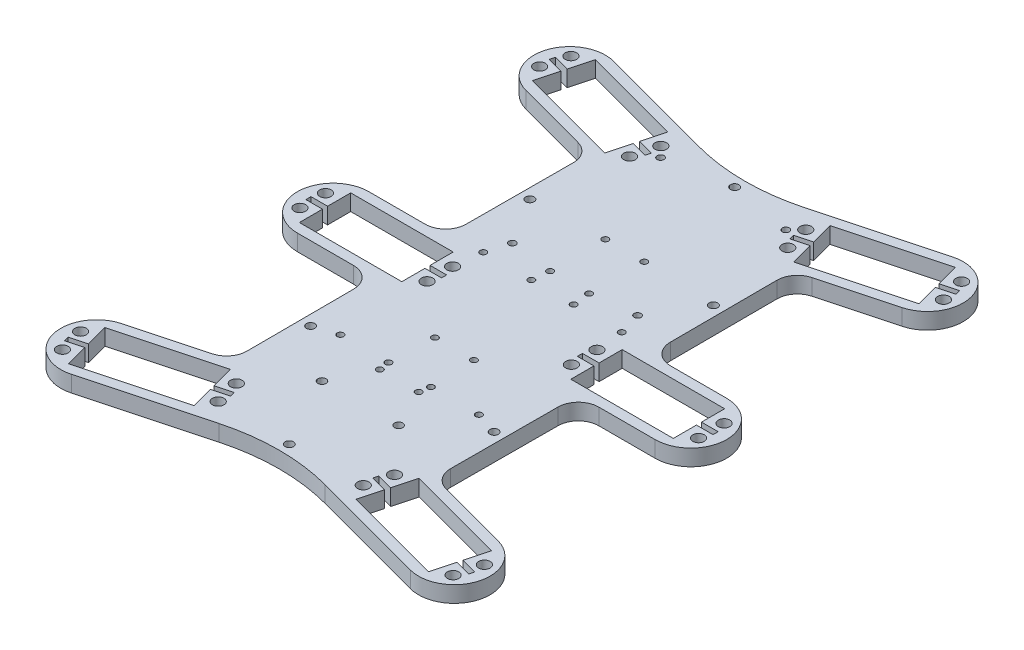
SolidWorks part; units mm, degrees
ref_plane "Front Plane" through (0, 0, 0) normal (0, 0, 1) x (1, 0, 0)
ref_plane "Top Plane" through (0, 0, 0) normal (0, 1, 0) x (1, 0, 0)
ref_plane "Right Plane" through (0, 0, 0) normal (1, 0, 0) x (0, 0, -1)
sketch "Sketch1" plane through (0, 0, 0) normal (0, 1, 0) x (1, 0, 0)
  line L0 (0, 32.1883) -> (0, -21.4181) construction
  line L1 (0, 0) -> (27.1703, 0) construction
  line L2 (-70, 14) -> (-40, 14)
  line L3 (-40, 14) -> (-39.8161, 70)
  line L4 (-39.8161, 70) -> (-73.6235, 79.0587)
  line L5 (-66.3765, 106.1046) -> (0, 88.3191)
  line L10 (-66.3765, 106.1046) -> (-73.6235, 79.0587) construction
  line L12 (-70, 14) -> (-70, -14) construction
  line L14 (-66.3765, -106.1046) -> (0, -88.3191)
  line L15 (-39.8161, -70) -> (-73.6235, -79.0587)
  line L16 (-40, -14) -> (-39.8161, -70)
  line L17 (-70, -14) -> (-40, -14)
  line L18 (66.3765, -106.1046) -> (0, -88.3191)
  line L19 (66.3765, 106.1046) -> (0, 88.3191)
  line L20 (70, 14) -> (70, -14) construction
  line L21 (66.3765, 106.1046) -> (73.6235, 79.0587) construction
  line L22 (70, -14) -> (40, -14)
  line L23 (40, -14) -> (39.8161, -70)
  line L24 (39.8161, -70) -> (73.6235, -79.0587)
  line L25 (39.8161, 70) -> (73.6235, 79.0587)
  line L26 (40, 14) -> (39.8161, 70)
  line L27 (70, 14) -> (40, 14)
  line L28 (-70.4609, 103.1096) -> (-75.6631, 83.6945)
  line L29 (-75.6631, 83.6945) -> (-36.9295, 73.3159)
  line L30 (-36.9295, 73.3159) -> (-31.7272, 92.731)
  line L31 (-31.7272, 92.731) -> (-70.4609, 103.1096)
  line L32 (-51.094, 97.9203) -> (-56.2963, 78.5052) construction
  line L33 (-70, 92.5816) -> (-73.062, 93.4021) construction
  line L34 (-53.12, 10.05) -> (-53.12, -10.05) construction
  line L35 (-73.17, 10.05) -> (-33.07, 10.05)
  line L36 (-73.17, 10.05) -> (-73.17, -10.05)
  line L37 (-73.17, -10.05) -> (-33.07, -10.05)
  line L38 (-33.07, 10.05) -> (-33.07, -10.05)
  line L39 (-73.17, 10.05) -> (-33.07, -10.05) construction
  line L40 (-73.17, -10.05) -> (-33.07, 10.05) construction
  line L41 (-36.9295, -73.3159) -> (-31.7272, -92.731)
  line L42 (-31.7272, -92.731) -> (-70.4609, -103.1096)
  line L43 (-70.4609, -103.1096) -> (-75.6631, -83.6945)
  line L44 (-75.6631, -83.6945) -> (-36.9295, -73.3159)
  line L45 (36.9295, 73.3159) -> (31.7272, 92.731)
  line L46 (75.6631, 83.6945) -> (36.9295, 73.3159)
  line L47 (70.4609, 103.1096) -> (75.6631, 83.6945)
  line L48 (31.7272, 92.731) -> (70.4609, 103.1096)
  line L49 (73.17, -10.05) -> (33.07, 10.05) construction
  line L50 (73.17, 10.05) -> (33.07, -10.05) construction
  line L51 (53.12, 10.05) -> (53.12, -10.05) construction
  line L52 (33.07, 10.05) -> (33.07, -10.05)
  line L53 (73.17, -10.05) -> (33.07, -10.05)
  line L54 (73.17, 10.05) -> (73.17, -10.05)
  line L55 (73.17, 10.05) -> (33.07, 10.05)
  line L56 (36.9295, -73.3159) -> (31.7272, -92.731)
  line L57 (75.6631, -83.6945) -> (36.9295, -73.3159)
  line L58 (31.7272, -92.731) -> (70.4609, -103.1096)
  line L59 (70.4609, -103.1096) -> (75.6631, -83.6945)
  line L60 (-76.4333, 99.4818) -> (-79.0215, 89.8226) construction
  line L61 (-77.7274, 94.6522) -> (-70, 92.5816) construction
  line L62 (-78, 5) -> (-78, -5) construction
  arc A0 (-70, 14) -> (-70, -14) centre (-70, 0) ccw
  arc A1 (-66.3765, 106.1046) -> (-73.6235, 79.0587) centre (-70, 92.5816) ccw
  circle A8 centre (-76.4333, 99.4818) radius 2.25
  circle A9 centre (-79.0215, 89.8226) radius 2.25
  circle A10 centre (-78, 5) radius 2.25
  arc A11 (-66.3765, -106.1046) -> (-73.6235, -79.0587) centre (-70, -92.5816) cw
  circle A12 centre (-79.0215, -89.8226) radius 2.25
  circle A13 centre (-76.4333, -99.4818) radius 2.25
  circle A14 centre (-78, -5) radius 2.25
  circle A15 centre (78, -5) radius 2.25
  circle A16 centre (76.4333, -99.4818) radius 2.25
  circle A17 centre (79.0215, -89.8226) radius 2.25
  arc A18 (66.3765, -106.1046) -> (73.6235, -79.0587) centre (70, -92.5816) ccw
  circle A19 centre (78, 5) radius 2.25
  circle A20 centre (79.0215, 89.8226) radius 2.25
  circle A21 centre (76.4333, 99.4818) radius 2.25
  arc A22 (66.3765, 106.1046) -> (73.6235, 79.0587) centre (70, 92.5816) cw
  arc A23 (70, 14) -> (70, -14) centre (70, 0) cw
  circle A24 centre (-30.957, 76.9437) radius 2.25
  circle A25 centre (-28.3688, 86.603) radius 2.25
  circle A26 centre (-28.24, -5) radius 2.25
  circle A27 centre (-28.24, 5) radius 2.25
  circle A28 centre (-28.3688, -86.603) radius 2.25
  circle A29 centre (-30.957, -76.9437) radius 2.25
  circle A30 centre (28.3688, 86.603) radius 2.25
  circle A31 centre (30.957, 76.9437) radius 2.25
  circle A32 centre (28.24, 5) radius 2.25
  circle A33 centre (28.24, -5) radius 2.25
  circle A34 centre (30.957, -76.9437) radius 2.25
  circle A35 centre (28.3688, -86.603) radius 2.25
  point P60 (-51.094, 97.9203)
  point P62 (-56.2963, 78.5052)
  point P65 (-73.062, 93.4021)
  point P71 (-53.12, 0)
  point P108 (53.12, 0)
  point P118 (-83.523, 96.2051)
  dimension "D2" = 14
  dimension "D3" = 10
  dimension "D8" = 4.5
  dimension "D1" = 75
  dimension "D4" = 70
  dimension "D5" = 30
  dimension "D6" = 35
  dimension "D7" = 56
  dimension "D9" = 8
  dimension "D10" = 5
  dimension "D11" = 10
  dimension "D12" = 40.1
  dimension "D13" = 20.1
  dimension "D14" = 4.83
  dimension "D15" = 40.1
  dimension "D16" = 20.1
  dimension "D17" = 4.83
  dimension "D18" = 8
extrude "Boss-Extrude1" add sketch "Sketch1" along normal blind 6.35
fillet "Fillet1" radius 80 2 edges at (0, 3.175, -88.3191) (0, 3.175, 88.3191)
fillet "Fillet2" radius 8 8 edges at (39.8161, 3.175, 70) (40, 3.175, 14) (40, 3.175, -14) (39.8161, 3.175, -70) (-39.8161, 3.175, -70) (-40, 3.175, -14) (-40, 3.175, 14) (-39.8161, 3.175, 70)
sketch "Sketch5" plane through (0, 6.35, 0) normal (0, 1, 0) x (1, 0, 0)
  line L0 (0, 91.1411) -> (0, -91.1411) construction
  line L1 (-84, 0) -> (84, 0) construction
  line L2 (-33.07, -10.05) -> (-33.07, 10.05) construction
  line L3 (-33.07, 1) -> (-26.57, 1)
  line L4 (-33.07, 1) -> (-33.07, -1)
  line L5 (-33.07, -1) -> (-26.57, -1)
  line L6 (-26.57, 1) -> (-26.57, -1)
  line L7 (-33.07, 1) -> (-26.57, -1) construction
  line L8 (-33.07, -1) -> (-26.57, 1) construction
  line L9 (-33.07, 10.05) -> (-73.17, 10.05) construction
  line L10 (-53.12, 10.05) -> (-53.12, -10.05) construction
  line L11 (-73.17, -10.05) -> (-33.07, -10.05) construction
  line L12 (-73.17, -1) -> (-79.67, 1) construction
  line L13 (-73.17, 1) -> (-79.67, -1) construction
  line L14 (-79.67, 1) -> (-79.67, -1)
  line L15 (-73.17, -1) -> (-79.67, -1)
  line L16 (-73.17, 1) -> (-73.17, -1)
  line L17 (-73.17, 1) -> (-79.67, 1)
  line L18 (-34.0695, 83.9894) -> (-27.791, 82.307)
  line L19 (-36.9295, 73.3159) -> (-31.7272, 92.731) construction
  line L20 (-27.791, 82.307) -> (-28.3087, 80.3752)
  line L21 (-28.3087, 80.3752) -> (-34.5872, 82.0575)
  line L22 (-34.0695, 83.9894) -> (-34.5872, 82.0575)
  line L23 (-51.094, 97.9203) -> (-56.2963, 78.5052) construction
  line L24 (-31.7272, 92.731) -> (-70.4609, 103.1096) construction
  line L25 (-75.6631, 83.6945) -> (-36.9295, 73.3159) construction
  line L26 (-72.8032, 94.368) -> (-73.3208, 92.4362)
  line L27 (-79.5993, 94.1185) -> (-73.3208, 92.4362)
  line L28 (-79.0817, 96.0503) -> (-79.5993, 94.1185)
  line L29 (-72.8032, 94.368) -> (-79.0817, 96.0503)
  line L30 (51.094, 97.9203) -> (56.2963, 78.5052) construction
  line L31 (72.8032, 94.368) -> (79.0817, 96.0503)
  line L32 (79.0817, 96.0503) -> (79.5993, 94.1185)
  line L33 (79.5993, 94.1185) -> (73.3208, 92.4362)
  line L34 (72.8032, 94.368) -> (73.3208, 92.4362)
  line L35 (34.0695, 83.9894) -> (34.5872, 82.0575)
  line L36 (28.3087, 80.3752) -> (34.5872, 82.0575)
  line L37 (27.791, 82.307) -> (28.3087, 80.3752)
  line L38 (34.0695, 83.9894) -> (27.791, 82.307)
  line L39 (73.17, 1) -> (79.67, -1) construction
  line L40 (73.17, -1) -> (79.67, 1) construction
  line L41 (53.12, 10.05) -> (53.12, -10.05) construction
  line L42 (33.07, -1) -> (26.57, 1) construction
  line L43 (33.07, 1) -> (26.57, -1) construction
  line L44 (73.17, 1) -> (79.67, 1)
  line L45 (73.17, 1) -> (73.17, -1)
  line L46 (73.17, -1) -> (79.67, -1)
  line L47 (79.67, 1) -> (79.67, -1)
  line L48 (26.57, 1) -> (26.57, -1)
  line L49 (33.07, -1) -> (26.57, -1)
  line L50 (33.07, 1) -> (33.07, -1)
  line L51 (33.07, 1) -> (26.57, 1)
  line L52 (51.094, -97.9203) -> (56.2963, -78.5052) construction
  line L53 (-51.094, -97.9203) -> (-56.2963, -78.5052) construction
  line L54 (34.0695, -83.9894) -> (27.791, -82.307)
  line L55 (27.791, -82.307) -> (28.3087, -80.3752)
  line L56 (28.3087, -80.3752) -> (34.5872, -82.0575)
  line L57 (34.0695, -83.9894) -> (34.5872, -82.0575)
  line L58 (72.8032, -94.368) -> (73.3208, -92.4362)
  line L59 (79.5993, -94.1185) -> (73.3208, -92.4362)
  line L60 (79.0817, -96.0503) -> (79.5993, -94.1185)
  line L61 (72.8032, -94.368) -> (79.0817, -96.0503)
  line L62 (-72.8032, -94.368) -> (-79.0817, -96.0503)
  line L63 (-79.0817, -96.0503) -> (-79.5993, -94.1185)
  line L64 (-79.5993, -94.1185) -> (-73.3208, -92.4362)
  line L65 (-72.8032, -94.368) -> (-73.3208, -92.4362)
  line L66 (-34.0695, -83.9894) -> (-34.5872, -82.0575)
  line L67 (-28.3087, -80.3752) -> (-34.5872, -82.0575)
  line L68 (-27.791, -82.307) -> (-28.3087, -80.3752)
  line L69 (-34.0695, -83.9894) -> (-27.791, -82.307)
  arc A0 (-20.7055, 93.8671) -> (20.7055, 93.8671) centre (0, 171.1411) ccw construction
  arc A1 (20.7055, -93.8671) -> (-20.7055, -93.8671) centre (0, -171.1411) ccw construction
  arc A2 (-70, 14) -> (-70, -14) centre (-70, 0) ccw construction
  arc A3 (70, -14) -> (70, 14) centre (70, 0) ccw construction
  point P16 (-29.82, 0)
  point P23 (-53.12, 10.05)
  point P34 (-76.42, 0)
  point P39 (-34.3284, 83.0234)
  point P42 (-34.3284, 83.0234)
  point P53 (-73.062, 93.4021)
  point P64 (73.062, 93.4021)
  point P65 (34.3284, 83.0234)
  point P76 (76.42, 0)
  point P77 (29.82, 0)
  point P98 (34.3284, -83.0234)
  point P99 (73.062, -93.4021)
  point P100 (-73.062, -93.4021)
  point P101 (-34.3284, -83.0234)
  dimension "D1" = 2
  dimension "D2" = 6.5
  dimension "D3" = 2
  dimension "D4" = 6.5
extrude "Cut-Extrude2" cut sketch "Sketch5" against normal through all
sketch "Sketch6" plane through (0, 6.35, 0) normal (0, 1, 0) x (1, 0, 0)
  circle A0 centre (27.1, -40.0589) radius 1.25 construction
  circle A1 centre (8.3, -40.0589) radius 1.25 construction
  circle A2 centre (-8.3, -40.0589) radius 1.25 construction
  circle A3 centre (-27.1, -40.0589) radius 1.25 construction
  circle A4 centre (27.1, 15.8411) radius 1.25 construction
  circle A5 centre (-8.3, 15.8411) radius 1.25 construction
  circle A6 centre (-27.1, 15.8411) radius 1.25 construction
  circle A7 centre (-24.5, 24.6411) radius 1.35 construction
  circle A8 centre (24.5, 24.6411) radius 1.35 construction
  circle A9 centre (24.5, 82.6411) radius 1.35 construction
  circle A10 centre (-24.5, 82.6411) radius 1.35 construction
  circle A11 centre (27.1, -40.0589) radius 1.25
  circle A12 centre (8.3, -40.0589) radius 1.25
  circle A13 centre (-8.3, -40.0589) radius 1.25
  circle A14 centre (-27.1, -40.0589) radius 1.25
  circle A15 centre (27.1, 15.8411) radius 1.25
  circle A16 centre (-8.3, 15.8411) radius 1.25
  circle A17 centre (-27.1, 15.8411) radius 1.25
  circle A18 centre (-24.5, 24.6411) radius 1.35
  circle A19 centre (24.5, 24.6411) radius 1.35
  circle A20 centre (24.5, 82.6411) radius 1.35
  circle A21 centre (-24.5, 82.6411) radius 1.35
  circle A22 centre (8.3, 15.8411) radius 1.25 construction
  circle A23 centre (8.3, 15.8411) radius 1.25
extrude "Cut-Extrude3" cut sketch "Sketch6" against normal blind 10
sketch "Sketch7" plane through (0, 0, 0) normal (0, -1, 0) x (1, 0, 0)
  circle A0 centre (-7.62, 44.13) radius 1.25 construction
  circle A1 centre (7.62, 44.13) radius 1.25 construction
  circle A2 centre (7.62, 22.54) radius 1.25 construction
  circle A3 centre (-7.62, 22.54) radius 1.25 construction
  circle A4 centre (7.62, -22.54) radius 1.25 construction
  circle A5 centre (7.62, -44.13) radius 1.25 construction
  circle A6 centre (-7.62, -22.54) radius 1.25 construction
  circle A7 centre (-7.62, -44.13) radius 1.25 construction
  circle A8 centre (-7.62, 44.13) radius 1.25
  circle A9 centre (7.62, 44.13) radius 1.25
  circle A10 centre (7.62, 22.54) radius 1.25
  circle A11 centre (-7.62, 22.54) radius 1.25
  circle A12 centre (7.62, -22.54) radius 1.25
  circle A13 centre (7.62, -44.13) radius 1.25
  circle A14 centre (-7.62, -22.54) radius 1.25
  circle A15 centre (-7.62, -44.13) radius 1.25
extrude "Cut-Extrude4" cut sketch "Sketch7" against normal blind 10
sketch "Sketch8" plane through (0, 6.35, 0) normal (0, 1, 0) x (1, 0, 0)
  circle A0 centre (15, -59.3589) radius 1.6 construction
  circle A1 centre (-15, -59.3589) radius 1.6 construction
  circle A2 centre (15, -59.3589) radius 1.6
  circle A3 centre (-15, -59.3589) radius 1.6
extrude "Cut-Extrude5" cut sketch "Sketch8" against normal blind 10
sketch "Sketch10" plane through (0, 6.35, 0) normal (0, 1, 0) x (1, 0, 0)
  circle A0 centre (-35.905, 42.9071) radius 1.65 construction
  circle A1 centre (0, 87.1411) radius 1.65 construction
  circle A2 centre (35.905, 42.9071) radius 1.65 construction
  circle A3 centre (35.905, -42.9071) radius 1.65 construction
  circle A4 centre (-35.905, -42.9071) radius 1.65 construction
  circle A5 centre (0, -87.1411) radius 1.65 construction
  circle A6 centre (-35.905, 42.9071) radius 1.65
  circle A7 centre (0, 87.1411) radius 1.65
  circle A8 centre (35.905, 42.9071) radius 1.65
  circle A9 centre (35.905, -42.9071) radius 1.65
  circle A10 centre (-35.905, -42.9071) radius 1.65
  circle A11 centre (0, -87.1411) radius 1.65
extrude "Cut-Extrude6" cut sketch "Sketch10" against normal blind 10
